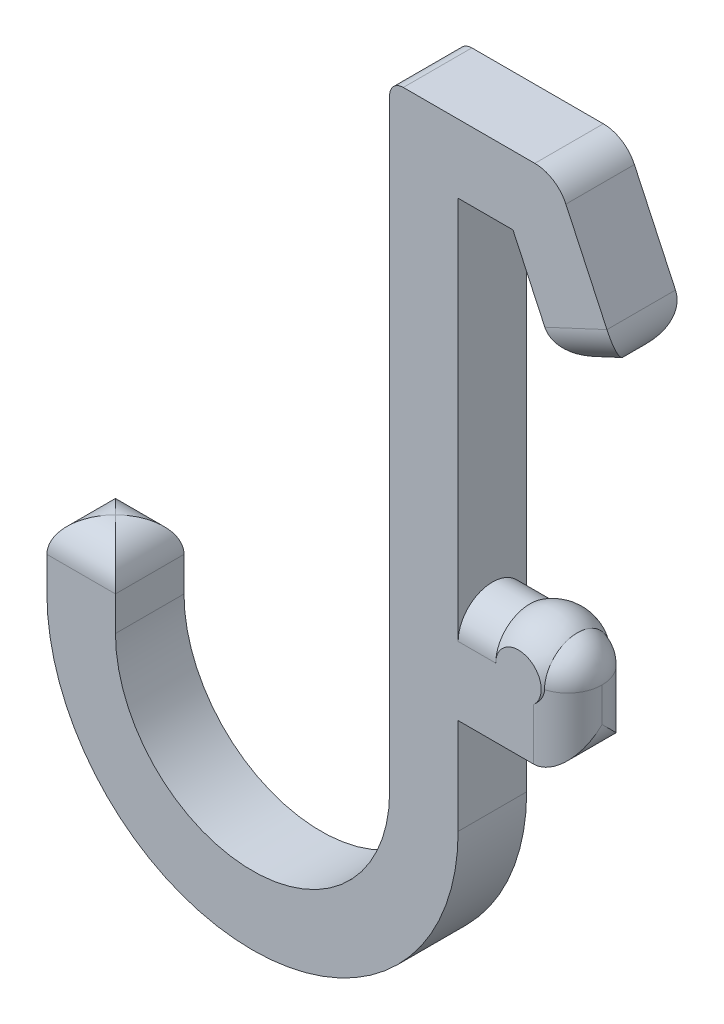
SolidWorks part; units mm, degrees
ref_plane "前视基准面" through (0, 0, 0) normal (0, 0, 1) x (1, 0, 0)
ref_plane "上视基准面" through (0, 0, 0) normal (0, 1, 0) x (1, 0, 0)
ref_plane "右视基准面" through (0, 0, 0) normal (1, 0, 0) x (0, 0, -1)
sketch "草图1" plane through (0, 0, 0) normal (0, 0, 1) x (1, 0, 0)
  line L0 (0, 0) -> (0, 28)
  line L1 (0, 28) -> (4, 28)
  line L2 (4, 28) -> (7.3809, 20.7495)
  line L3 (0, 0) -> (8, 0)
  line L4 (8, 0) -> (8, -5)
  line L5 (8, -5) -> (0, -5)
  line L6 (7.3809, 20.7495) -> (11.9125, 22.8626)
  line L7 (11.9125, 22.8626) -> (7.1854, 33)
  line L8 (-5, 33) -> (7.1854, 33)
  line L9 (-5, 33) -> (-5, -12)
  line L10 (-25, -12) -> (-5, -12) construction
  line L11 (-25, -12) -> (-25, -7)
  line L12 (-25, -7) -> (-30, -7)
  line L13 (-30, -7) -> (-30, -12)
  line L14 (0, -5) -> (0, -12)
  arc A0 (-25, -12) -> (-5, -12) centre (-15, -12) ccw
  arc A1 (-30, -12) -> (0, -12) centre (-15, -12) ccw
  dimension "D11" = 10
  dimension "D1" = 4
  dimension "D2" = 65
  dimension "D3" = 28
  dimension "D4" = 8
  dimension "D5" = 5
  dimension "D6" = 5
  dimension "D7" = 5
  dimension "D8" = 45
  dimension "D9" = 5
  dimension "D10" = 8
  dimension "D12" = 5
  dimension "D13" = 5
extrude "凸台-拉伸1" add sketch "草图1" along normal blind 5
fillet "圆角1" radius 2.5 9 edges at (7.3809, 20.7495, 2.5) (9.6467, 21.8061, 5) (11.9125, 22.8626, 2.5) (9.6467, 21.8061, 0) (-25, -7, 2.5) (-27.5, -7, 5) (-30, -7, 2.5) (-27.5, -7, 0) (7.1854, 33, 2.5)
fillet "圆角2" radius 1 1 edges at (-5, 33, 2.5)
sketch "草图3" plane through (0, 0, 0) normal (1, 0, 0) x (0, 0, -1)
  line L0 (-5, 0) -> (0, 0) construction
  line L1 (-5, 0) -> (0, 0)
  arc A0 (0, 0) -> (-5, 0) centre (-2.5, 0) ccw
extrude "凸台-拉伸2" add sketch "草图3" along normal up to surface (8 mm away) up to face at (8, -2.5, 2.5)
fillet "圆角3" radius 2.5 4 edges at (8, -2.5, 5) (8, -2.5, 0) (8, -5, 2.5) (8, 2.5, 2.5)
ref_plane "基准面1" through (4.4, 0, 0) normal (1, 0, 0) x (0, 0, -1)
sketch "草图4" plane through (4.4, 0, 0) normal (1, 0, 0) x (0, 0, -1)
  line L0 (-2.5, 0) -> (0.5, 0) construction
  line L1 (-5.5, 0) -> (0.5, 0)
  arc A0 (0.5, 0) -> (-5.5, 0) centre (-2.5, 0) ccw
  point P4 (-2.5, 0)
  point P6 (0, 0)
revolve "旋转3" add sketch "草图4" angle 360 about L0
sketch "草图5" plane through (-5, 0, 0) normal (-1, 0, 0) x (0, 0, 1)
  line L0 (0, -2.0992) -> (-1.4678, -2.0992)
  line L1 (0, 32) -> (0, -12) construction
  line L2 (-1.4678, -2.0992) -> (-1.4678, 2.0791)
  line L3 (-1.4678, 2.0791) -> (0, 2.0791)
  line L4 (0, 2.0791) -> (0, -2.0992)
  line L5 (5, -2.0992) -> (6.3896, -2.0992)
  line L6 (5, 32) -> (5, -12) construction
  line L7 (6.3896, -2.0992) -> (6.3896, 2.0791)
  line L8 (6.3896, 2.0791) -> (5, 2.0791)
  line L9 (5, 2.0791) -> (5, -2.0992)
extrude "切除-拉伸1" cut sketch "草图5" against normal blind 20
